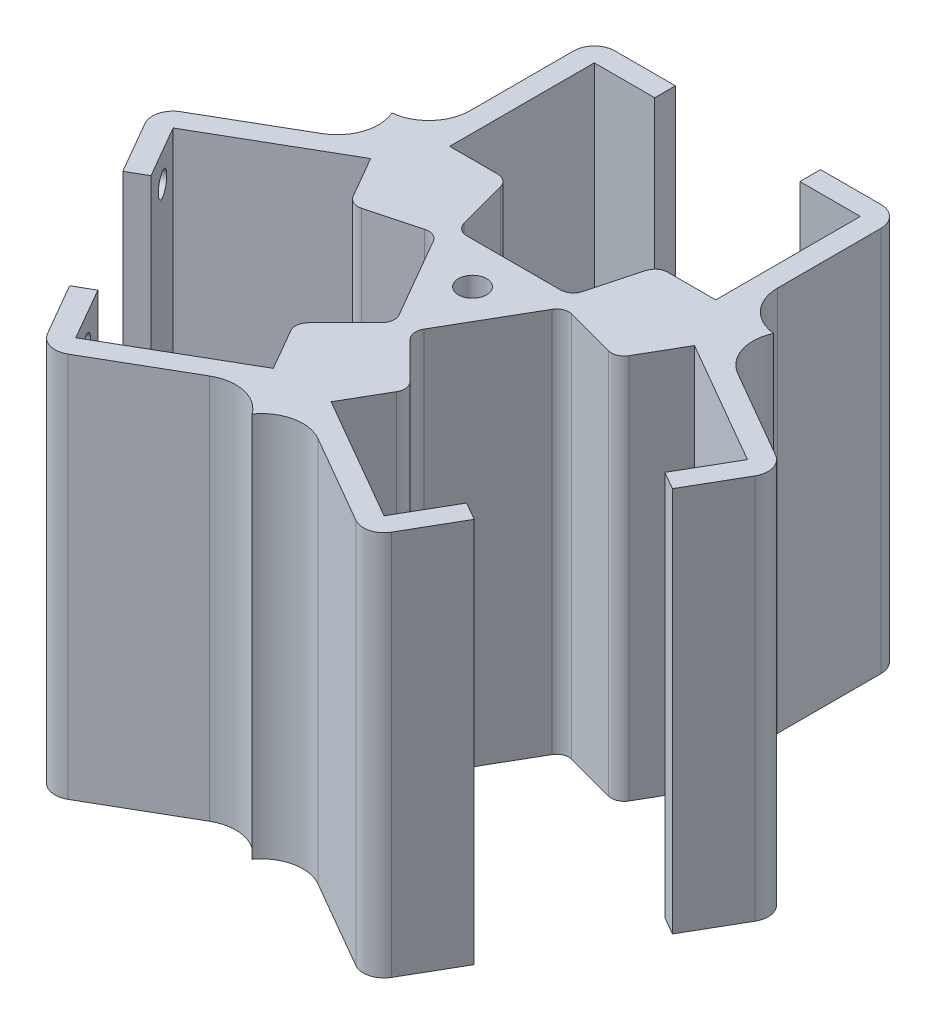
SolidWorks part; units mm, degrees
material "ABS"
ref_plane "Alzado" through (0, 0, 0) normal (0, 0, 1) x (1, 0, 0)
ref_plane "Planta" through (0, 0, 0) normal (0, 1, 0) x (1, 0, 0)
ref_plane "Vista lateral" through (0, 0, 0) normal (1, 0, 0) x (0, 0, -1)
sketch "Croquis1" plane through (0, 0, 0) normal (0, 1, 0) x (1, 0, 0)
  line L0 (0, 50.8) -> (0, -50.8) construction
  line L1 (-50.8, 0) -> (50.8, 0) construction
  line L2 (0, 0) -> (-35.921, -35.921) construction
  line L3 (0, 0) -> (35.921, -35.921) construction
  line L10 (0, -17.5) -> (-15.1554, 8.75) construction
  line L11 (-15.1554, 8.75) -> (15.1554, 8.75) construction
  line L12 (15.1554, 8.75) -> (0, -17.5) construction
  line L13 (-1.2978, -16.7522) -> (-15.1813, 7.2027) construction
  line L14 (1.2978, -16.7522) -> (15.1813, 7.2027) construction
  line L15 (-13.8835, 9.4549) -> (13.8835, 9.4549) construction
  line L16 (1.6964, -16.0645) -> (13.335, -27.7031)
  line L17 (13.335, -27.7031) -> (0, -50.8)
  line L18 (0, -50.8) -> (-13.335, -27.7031)
  line L19 (-13.335, -27.7031) -> (-1.6964, -16.0645)
  line L20 (-17.3241, 25.4) -> (-13.0641, 9.5013)
  line L21 (-43.9941, 25.4) -> (-17.3241, 25.4)
  line L22 (-30.6591, 2.3031) -> (-43.9941, 25.4)
  line L23 (-14.7604, 6.5631) -> (-30.6591, 2.3031)
  line L24 (30.6591, 2.3031) -> (14.7604, 6.5631)
  line L25 (43.9941, 25.4) -> (30.6591, 2.3031)
  line L26 (17.3241, 25.4) -> (43.9941, 25.4)
  line L27 (13.0641, 9.5013) -> (17.3241, 25.4)
  line L28 (-14.7604, 6.5631) -> (-1.6964, -16.0645)
  line L29 (1.6964, -16.0645) -> (14.7604, 6.5631)
  line L30 (-13.0641, 9.5013) -> (13.0641, 9.5013)
  line L31 (-43.9941, 25.4) -> (0, -50.8) construction
  line L32 (43.9941, 25.4) -> (0, -50.8) construction
  line L33 (-43.9941, 25.4) -> (43.9941, 25.4) construction
  circle A0 centre (0, 0) radius 50.8 construction
  circle A7 centre (0, 0) radius 17.5 construction
  circle A8 centre (-13.8835, 7.9549) radius 1.5 construction
  circle A9 centre (13.8835, 7.9549) radius 1.5 construction
  circle A10 centre (0, -16) radius 1.5 construction
  arc A11 (-15.1813, 7.2027) -> (-13.8835, 9.4549) centre (-13.8835, 7.9549) cw construction
  arc A12 (15.1813, 7.2027) -> (13.8835, 9.4549) centre (13.8835, 7.9549) ccw construction
  arc A13 (1.2978, -16.7522) -> (-1.2978, -16.7522) centre (0, -16) cw construction
  arc A14 (-15.1813, 7.2027) -> (-13.8835, 9.4549) centre (-13.8835, 7.9549) cw construction
  arc A15 (13.8835, 9.4549) -> (15.1813, 7.2027) centre (13.8835, 7.9549) cw construction
  arc A16 (-1.2978, -16.7522) -> (1.2978, -16.7522) centre (0, -16) ccw construction
  circle A17 centre (0, 0) radius 76.2 construction
  point P45 (0, 0)
  dimension "D1" = 101.6
  dimension "D6" = 13.8835
  dimension "D9" = 3
  dimension "D5" = 3
  dimension "D4" = 35
  dimension "D10" = 152.4
  dimension "D2" = 45
  dimension "D3" = 45
  dimension "D7" = 26.67
extrude "Saliente-Extruir1" add sketch "Croquis1" along normal blind 88.9
sketch "Croquis4" plane through (0, 88.9, 0) normal (0, 1, 0) x (1, 0, 0)
  circle A0 centre (0, 0) radius 3.25
  dimension "D1" = 6.5
extrude "Cortar-Extruir1" cut sketch "Croquis4" against normal through all
fillet "Redondeo6" radius 3 5 edges at (-14.7604, 44.45, -6.5631) (1.6964, 44.45, 16.0645) (-1.6964, 44.45, 16.0645) (-13.0641, 44.45, -9.5013) (13.0641, 44.45, -9.5013)
fillet "Redondeo7" radius 3 6 edges at (-17.3241, 44.45, -25.4) (-30.6591, 44.45, -2.3031) (17.3241, 44.45, -25.4) (-13.335, 44.45, 27.7031) (30.6591, 44.45, -2.3031) (13.335, 44.45, 27.7031)
scale "Escala2" scale about centroid uniform scaling yes scale factor 1.05
sketch "Croquis9" plane through (0, 91.1225, 0) normal (0, 1, 0) x (1, 0, 0)
  line L9 (0, 76.2) -> (0, -76.2) construction
  line L10 (76.2, 0) -> (-76.2, 0) construction
  line L41 (-37.1934, 26.6702) -> (-37.1934, 61.6702)
  line L42 (-69.5041, -2.9545) -> (-39.1932, 14.5455)
  line L43 (-20.607, 26.6702) -> (-46.1934, 26.6702) construction
  line L44 (-32.1934, 66.6702) -> (-17.5643, 66.6702)
  line L45 (-17.5643, 66.6702) -> (-17.5643, 61.6702)
  line L46 (-17.5643, 61.6702) -> (-32.1934, 61.6702)
  line L47 (-32.1934, 61.6702) -> (-32.1934, 26.6702)
  line L48 (-32.1934, 26.6702) -> (-37.1934, 26.6702)
  line L49 (32.1934, 61.6702) -> (32.1934, 26.6702)
  line L50 (17.5643, 61.6702) -> (32.1934, 61.6702)
  line L51 (17.5643, 66.6702) -> (17.5643, 61.6702)
  line L52 (32.1934, 66.6702) -> (17.5643, 66.6702)
  line L53 (37.1934, 26.6702) -> (37.1934, 61.6702)
  line L54 (32.1934, 26.6702) -> (37.1934, 26.6702)
  line L55 (39.1937, 14.5452) -> (41.6937, 18.8753)
  line L56 (41.6937, 18.8753) -> (72.0046, 1.3753)
  line L57 (73.8347, -5.4548) -> (66.5202, -18.124)
  line L58 (66.5202, -18.124) -> (62.1901, -15.624)
  line L59 (62.1901, -15.624) -> (69.5046, -2.9548)
  line L60 (69.5046, -2.9548) -> (39.1937, 14.5452)
  line L61 (37.3112, -58.7154) -> (7.0003, -41.2154)
  line L62 (7.0003, -41.2154) -> (4.5003, -45.5455)
  line L63 (4.5003, -45.5455) -> (34.8112, -63.0455)
  line L64 (41.6414, -61.2154) -> (48.9559, -48.5462)
  line L65 (48.9559, -48.5462) -> (44.6258, -46.0462)
  line L66 (44.6258, -46.0462) -> (37.3112, -58.7154)
  line L79 (-39.1937, 14.5452) -> (-41.6937, 18.8753) [skipped]
  line L80 (-39.1932, 14.5455) -> (-41.6932, 18.8756)
  line L81 (-41.6937, 18.8753) -> (-72.0046, 1.3753) [skipped]
  line L83 (-41.6932, 18.8756) -> (-72.0041, 1.3756)
  line L85 (-69.5046, -2.9548) -> (-39.1937, 14.5452) [skipped]
  line L86 (-62.1901, -15.624) -> (-69.5046, -2.9548) [skipped]
  line L87 (-66.5202, -18.124) -> (-62.1901, -15.624) [skipped]
  line L88 (-73.8347, -5.4548) -> (-66.5202, -18.124) [skipped]
  line L89 (-73.8342, -5.4545) -> (-66.5197, -18.1237)
  line L90 (-66.5197, -18.1237) -> (-62.1896, -15.6237)
  line L91 (-62.1896, -15.6237) -> (-69.5041, -2.9545)
  line L92 (-46.1934, 26.6702) -> (-33.4002, 4.5117) construction
  line L93 (-7.0003, -41.2154) -> (-4.5003, -45.5455) [skipped]
  line L94 (-4.5003, -45.5455) -> (-34.8112, -63.0455) [skipped]
  line L95 (-41.6414, -61.2154) -> (-48.9559, -48.5462) [skipped]
  line L96 (-48.9559, -48.5462) -> (-44.6258, -46.0462) [skipped]
  line L97 (-44.6258, -46.0462) -> (-37.3112, -58.7154) [skipped]
  line L98 (-37.3112, -58.7154) -> (-7.0003, -41.2154) [skipped]
  line L99 (-6.9998, -41.2151) -> (-4.4998, -45.5452)
  line L100 (-4.4998, -45.5452) -> (-34.8107, -63.0452)
  line L101 (-41.6408, -61.2151) -> (-48.9554, -48.5459)
  line L102 (-48.9554, -48.5459) -> (-44.6253, -46.0459)
  line L103 (-44.6253, -46.0459) -> (-37.3107, -58.7151)
  line L104 (-37.3107, -58.7151) -> (-6.9998, -41.2151)
  line L105 (-12.7928, -31.1813) -> (0.0004, -53.3398) construction
  circle A0 centre (0, 0) radius 101.6 construction
  circle A1 centre (0, 0) radius 76.2 construction
  arc A8 (-37.1934, 61.6702) -> (-32.1934, 66.6702) centre (-32.1934, 61.6702) cw
  arc A9 (37.1934, 61.6702) -> (32.1934, 66.6702) centre (32.1934, 61.6702) ccw
  arc A10 (72.0046, 1.3753) -> (73.8347, -5.4548) centre (69.5046, -2.9548) cw
  arc A11 (34.8112, -63.0455) -> (41.6414, -61.2154) centre (37.3112, -58.7154) ccw
  arc A14 (-72.0046, 1.3753) -> (-73.8347, -5.4548) centre (-69.5046, -2.9548) ccw [skipped]
  arc A15 (-72.0041, 1.3756) -> (-73.8342, -5.4545) centre (-69.5041, -2.9545) ccw
  arc A16 (-34.8112, -63.0455) -> (-41.6414, -61.2154) centre (-37.3112, -58.7154) cw [skipped]
  arc A17 (-34.8107, -63.0452) -> (-41.6408, -61.2151) centre (-37.3107, -58.7151) cw
  point P55 (0.0002, 0.0003)
  point P56 (-1.3626, -0.7865)
  point P58 (0, 0)
  point P61 (0.0002, 0.0003)
  dimension "D1" = 152.4
  dimension "D2" = 203.2
  dimension "D3" = 5
  dimension "D9" = 2
  dimension "D4" = 9
  dimension "D5" = 35
  dimension "D6" = 3
  dimension "D7" = 2
extrude "Saliente-Extruir2" add sketch "Croquis9" against normal through all
fillet "Redondeo8" radius 10 1 edges at (-37.1934, 44.45, -26.6702)
fillet "Redondeo9" radius 10 1 edges at (37.1934, 44.45, -26.6702)
fillet "Redondeo12" radius 10 1 edges at (4.5004, 44.45, 45.5456)
fillet "Redondeo13" radius 10 1 edges at (41.6938, 44.45, -18.8753)
fillet "Redondeo14" radius 10 1 edges at (-4.4998, 44.45, 45.5452)
fillet "Redondeo16" radius 10 1 edges at (-41.6932, 44.45, -18.8756)
fillet "Redondeo17" radius 3 1 edges at (15.4988, 44.45, -6.8915)
sketch "Croquis20" plane through (-57.7375, 0, 33.3348) normal (-0.866, 0, 0.5) x (0.5, 0, 0.866)
  line L0 (32.1934, -2.2225) -> (32.1934, 91.1225) construction
  line L2 (17.5643, 91.1225) -> (32.1934, 91.1225) construction
  circle A0 centre (25.1934, 4.7775) radius 2.78
  circle A1 centre (25.1934, 84.1225) radius 2.78
  circle A2 centre (-25.1934, 84.1225) radius 2.78
  circle A3 centre (-25.1934, 4.7775) radius 2.78
  point P13 (24.8788, 91.1225)
  dimension "D1" = 5.56
  dimension "D2" = 7
  dimension "D3" = 7
  dimension "D4" = 7
  dimension "D5" = 7
extrude "Cortar-Extruir7" cut sketch "Croquis20" against normal blind 10
scale "Escala3" scale about centroid uniform scaling yes scale factor 0.9
sketch "Croquis22" plane through (0, 86.4552, 0) normal (0, 1, 0) x (1, 0, 0)
  circle A0 centre (0, 0) radius 76.2 construction
  circle A1 centre (0, 0) radius 101.6 construction
  dimension "D1" = 152.4
  dimension "D2" = 203.2
